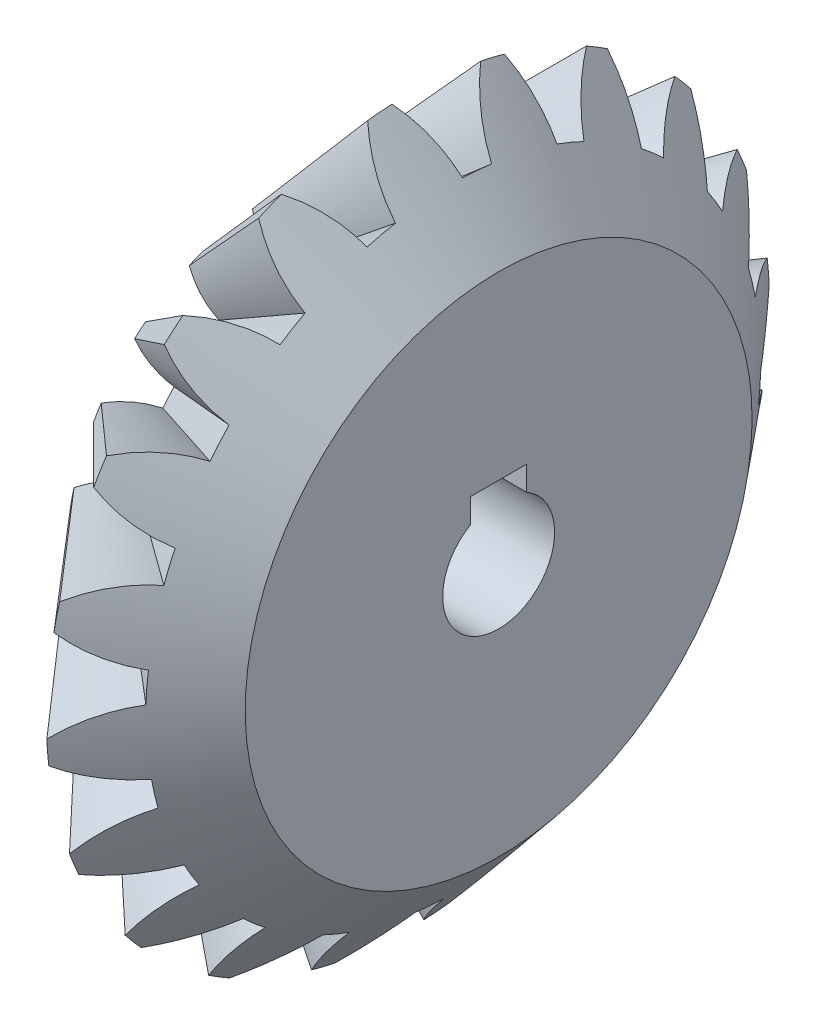
SolidWorks part; units mm, degrees
ref_plane "Front Plane" through (0, 0, 0) normal (0, 0, 1) x (1, 0, 0)
ref_plane "Top Plane" through (0, 0, 0) normal (0, 1, 0) x (1, 0, 0)
ref_plane "Right Plane" through (0, 0, 0) normal (1, 0, 0) x (0, 0, -1)
sketch "Sketch2" plane through (0, 0, 0) normal (0, 0, 1) x (1, 0, 0)
  line L0 (0, 0) -> (-30, 0) construction
  line L1 (-30, 0) -> (0, 30) construction
  line L2 (0, 30) -> (0, 0) construction
  line L3 (0, 30) -> (25.173, 0) construction
  line L4 (25.173, 0) -> (0, 0) construction
  line L5 (0, 30) -> (-8.4989, 40.1285) construction
  line L6 (-30, 0) -> (-1.9284, 32.2981) construction
  line L7 (-30, 0) -> (2.314, 27.2422) construction
  line L8 (-1.9284, 32.2981) -> (6.1708, 22.646)
  line L9 (6.1708, 22.646) -> (6.1708, 0)
  line L10 (-1.9284, 32.2981) -> (-13.7363, 18.7124)
  line L11 (-13.7363, 18.7124) -> (-8.0652, 13.7834)
  line L12 (-8.0652, 13.7834) -> (-8.0652, 0)
  line L13 (-8.0652, 0) -> (6.1708, 0)
  dimension "D1" = 30
  dimension "D2" = 40
  dimension "30" = 30
  dimension "D3" = 3
  dimension "D4" = 3.6
  dimension "D5" = 6
  dimension "D6" = 18
  dimension "D8" = 3.6
revolve "Revolve1" add sketch "Sketch2" angle 360 about L0
ref_plane "Plane1" through (14.7721, 12.3953, 0) normal (0.766, 0.6428, 0) x (0, 0, -1)
sketch "Sketch3" plane through (14.7721, 12.3953, 0) normal (0.766, 0.6428, 0) x (0, 0, -1)
  line L0 (0, -16.1809) -> (0, 0) construction
  line L1 (0, 22.9813) -> (0, -16.1809) construction
  line L2 (0, -12.8114) -> (0, 23.1886) construction
  line L3 (0, -12.8114) -> (3.6794, 43.3258) construction
  circle A0 centre (0, -12.8114) radius 39 construction
  circle A1 centre (0, -12.8114) radius 36 construction
  circle A2 centre (0, -12.8114) radius 32.5 construction
  arc A3 (-8.559, 31.4409) -> (0.8267, 19.6781) centre (-12.9944, 18.276) cw
  arc A4 (14.2618, 29.9452) -> (3.4211, 19.5081) centre (16.9409, 16.3139) ccw
  arc A5 (14.2618, 29.9452) -> (-8.559, 31.4409) centre (0, -12.8114) ccw
  arc A6 (0.8267, 19.6781) -> (3.4211, 19.5081) centre (0, -12.8114) cw
  ellipse E0 centre (0, 1.2395) end of major axis (-32.2981, 1.2395) minor radius 24.7418 construction
  dimension "D1" = 78
  dimension "D2" = 72
  dimension "D3" = 65
  dimension "D4" = 3.75
  dimension "D5" = 1.3
sketch "Sketch5" plane through (0, 0, 0) normal (0, 0, 1) x (1, 0, 0)
  point P0 (-30, 0)
loft "Cut-Loft1" cut profiles "Sketch5", "Sketch3"
pattern_circular "CirPattern1" count 20 over 360 about axis through (-8.0652, 0, 0) along (1, 0, 0) of "Cut-Loft1"
sketch "Sketch6" plane through (-8.0652, 0, 0) normal (-1, 0, 0) x (0, 0, 1)
  line L0 (0, 30) -> (0, 0) construction
  line L2 (-2.5, 4.3301) -> (-2.5, 6.5)
  line L3 (-2.5, 6.5) -> (2.5, 6.5)
  line L4 (2.5, 4.3301) -> (2.5, 6.5)
  arc A0 (-2.5, 4.3301) -> (2.5, 4.3301) centre (0, 0) ccw
  dimension "D1" = 10
  dimension "D2" = 2.5
  dimension "D3" = 2.5
extrude "Cut-Extrude1" cut sketch "Sketch6" against normal blind 50
